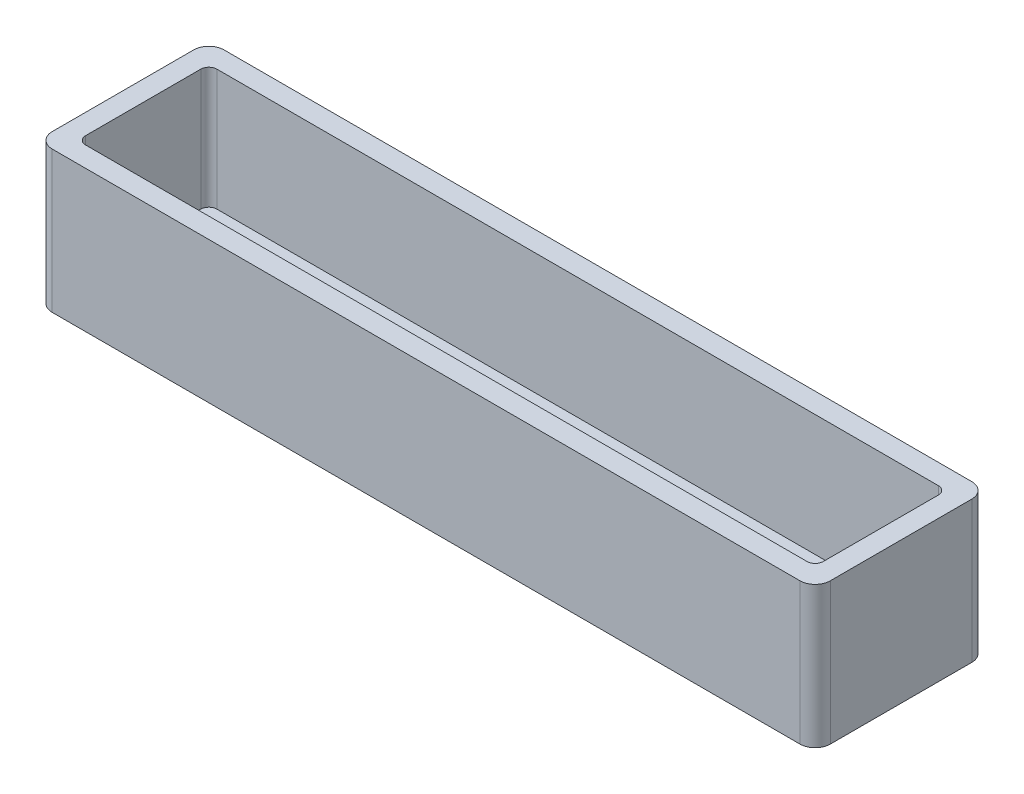
SolidWorks part; units mm, degrees
material "NEOPRENE"
ref_plane "Front" through (0, 0, 0) normal (0, 0, 1) x (1, 0, 0)
ref_plane "Top" through (0, 0, 0) normal (0, 1, 0) x (1, 0, 0)
ref_plane "Right" through (0, 0, 0) normal (1, 0, 0) x (0, 0, -1)
sketch "Sketch1" plane through (0, 0, 0) normal (0, 1, 0) x (1, 0, 0)
  line L0 (-115.8875, 0) -> (-122.2375, 0) construction
  line L1 (-122.2375, 26.9875) -> (122.2375, 26.9875)
  line L2 (-122.2375, 26.9875) -> (-122.2375, -26.9875)
  line L3 (-122.2375, -26.9875) -> (122.2375, -26.9875)
  line L4 (122.2375, 26.9875) -> (122.2375, -26.9875)
  line L5 (-122.2375, 26.9875) -> (122.2375, -26.9875) construction
  line L6 (-122.2375, -26.9875) -> (122.2375, 26.9875) construction
  line L7 (115.8875, 20.6375) -> (-115.8875, 20.6375)
  line L8 (115.8875, 20.6375) -> (115.8875, -20.6375)
  line L9 (115.8875, -20.6375) -> (-115.8875, -20.6375)
  line L10 (-115.8875, 20.6375) -> (-115.8875, -20.6375)
  line L11 (115.8875, 20.6375) -> (-115.8875, -20.6375) construction
  line L12 (115.8875, -20.6375) -> (-115.8875, 20.6375) construction
  line L13 (0, 20.6375) -> (0, 26.9875) construction
  point P0 (0, 0)
  point P6 (0, 0)
  dimension "D1" = 231.775
  dimension "D2" = 41.275
  dimension "D3" = 6.35
  dimension "THICKNESS" = 6.35
extrude "Boss-Extrude1" add sketch "Sketch1" along normal blind 38.1
sketch "Sketch2" plane through (0, 0, 0) normal (0, -1, 0) x (1, 0, 0)
  line L0 (99.6375, 0) -> (68.6375, 0) construction
  line L4 (122.2375, -26.9875) -> (122.2375, 26.9875)
  line L5 (122.2375, 26.9875) -> (-122.2375, 26.9875)
  line L6 (-122.2375, 26.9875) -> (-122.2375, -26.9875)
  line L7 (-122.2375, -26.9875) -> (122.2375, -26.9875)
  line L8 (122.2375, -26.9875) -> (122.2375, 26.9875)
  line L9 (122.2375, 26.9875) -> (-122.2375, 26.9875)
  line L10 (-122.2375, 26.9875) -> (-122.2375, -26.9875)
  line L11 (-122.2375, -26.9875) -> (122.2375, -26.9875)
  arc A0 (99.6375, -2.1) -> (99.6375, 2.1) centre (99.6375, 0) ccw construction
  arc A1 (99.6375, 2.1) -> (99.6375, -2.1) centre (99.6375, 0) ccw construction
  arc A2 (68.6375, -2.1) -> (68.6375, 2.1) centre (68.6375, 0) ccw construction
  arc A3 (68.6375, 2.1) -> (68.6375, -2.1) centre (68.6375, 0) ccw construction
  arc A4 (99.6375, -2.1) -> (99.6375, 2.1) centre (99.6375, 0) ccw
  arc A5 (99.6375, 2.1) -> (99.6375, -2.1) centre (99.6375, 0) ccw
  arc A6 (68.6375, -2.1) -> (68.6375, 2.1) centre (68.6375, 0) ccw
  arc A7 (68.6375, 2.1) -> (68.6375, -2.1) centre (68.6375, 0) ccw
  circle A8 centre (84.1375, 0) radius 12.065
  dimension "D2" = 24.13
  dimension "D1" = 0
extrude "Boss-Extrude2" add sketch "Sketch2" along normal blind 6.35
fillet "Fillet1" radius 2.54 4 edges at (115.8875, 19.05, -20.6375) (115.8875, 19.05, 20.6375) (-115.8875, 19.05, 20.6375) (-115.8875, 19.05, -20.6375)
fillet "Fillet2" radius 4.7625 4 edges at (-122.2375, 15.875, -26.9875) (122.2375, 15.875, -26.9875) (122.2375, 15.875, 26.9875) (-122.2375, 15.875, 26.9875)
sketch "Sketch6" [suppressed] plane through (0, -6.35, 0) normal (0, -1, 0) x (1, 0, 0)
  circle A0 centre (68.6375, 0) radius 2.1 construction
  circle A1 centre (68.6375, 0) radius 2.1
  circle A2 centre (99.6375, 0) radius 2.1 construction
  circle A3 centre (99.6375, 0) radius 2.1
extrude "Boss-Extrude4" [suppressed] add sketch "Sketch6" against normal up to surface (6.35 mm away) up to face at (68.6375, 0, -2.1)
sketch "Sketch7" [suppressed] plane through (0, -6.35, 0) normal (0, -1, 0) x (1, 0, 0)
  circle A0 centre (-45.2, 0.936) radius 4.445
  circle A1 centre (45, 0.936) radius 4.445
  dimension "D1" = 8.89
extrude "Cut-Extrude3" [suppressed] cut sketch "Sketch7" against normal through all
sketch "Sketch8" [suppressed] plane through (0, 38.1, 0) normal (0, 1, 0) x (1, 0, 0)
  line L25 (-156.7727, 50.8) -> (156.7727, 50.8)
  line L26 (-156.7727, 50.8) -> (-156.7727, -50.8)
  line L27 (-156.7727, -50.8) -> (156.7727, -50.8)
  line L28 (156.7727, 50.8) -> (156.7727, -50.8)
  line L29 (-156.7727, 50.8) -> (156.7727, -50.8) construction
  line L30 (-156.7727, -50.8) -> (156.7727, 50.8) construction
  point P15 (0, 0)
  dimension "D2" = 101.6
  dimension "D1" = 313.5454
extrude "Cut-Extrude4" [suppressed] cut sketch "Sketch8" against normal blind 9.525
equation "\"D1@Boss-Extrude2\"=\"THICKNESS\""
